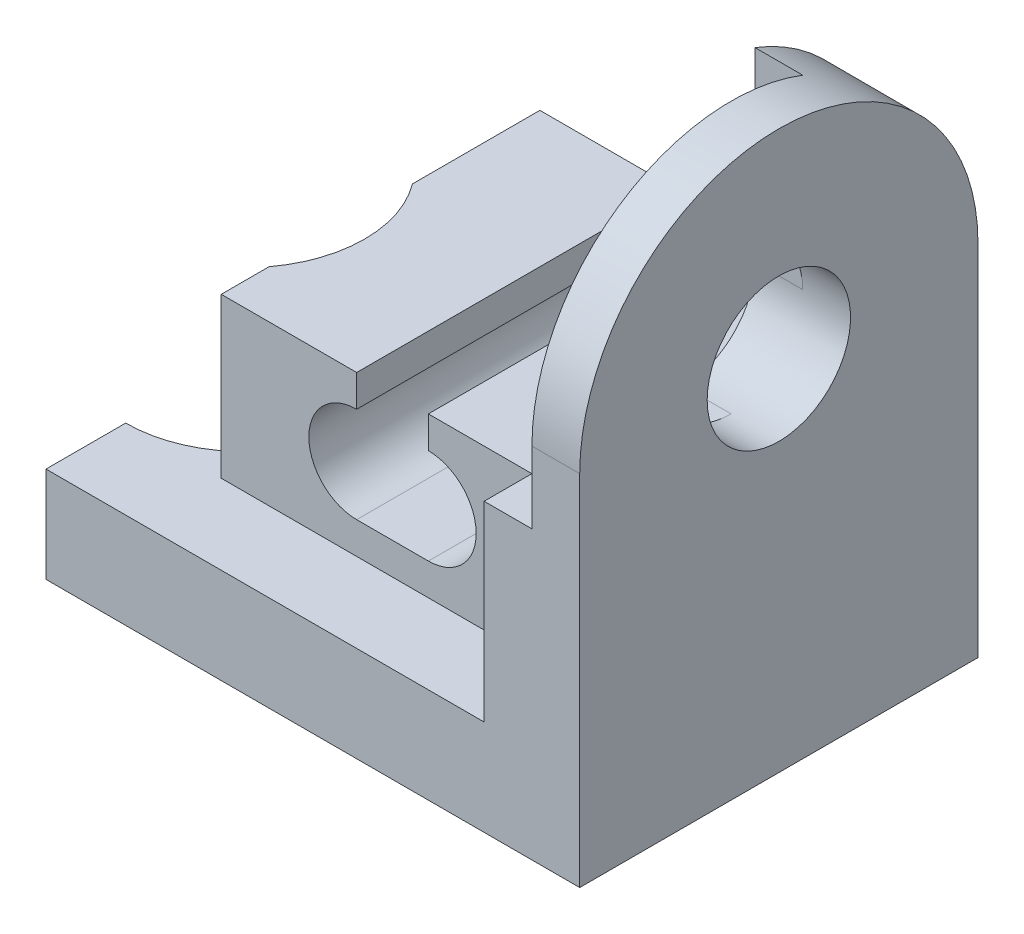
SolidWorks part; units mm, degrees
ref_plane "Front Plane" through (0, 0, 0) normal (0, 0, 1) x (1, 0, 0)
ref_plane "Top Plane" through (0, 0, 0) normal (0, 1, 0) x (1, 0, 0)
ref_plane "Right Plane" through (0, 0, 0) normal (1, 0, 0) x (0, 0, -1)
sketch "Sketch1" plane through (0, 0, 0) normal (0, 0, 1) x (1, 0, 0)
  line L0 (-38, 22) -> (-32, 22) construction
  line L1 (0, 0) -> (-67, 0)
  line L2 (0, 0) -> (0, 10.4431)
  line L3 (-12, 12) -> (-67, 12)
  line L4 (-67, 0) -> (-67, 12)
  line L5 (0, 0) -> (-14.6824, 0)
  line L6 (0, 0) -> (0, 70)
  line L7 (0, 70) -> (-12, 70)
  line L8 (-12, 12) -> (-12, 70)
  line L9 (-12, 12) -> (-55, 12)
  line L10 (-12, 12) -> (-12, 32)
  line L11 (-12, 32) -> (-29, 32)
  line L12 (-55, 12) -> (-55, 32)
  line L15 (-37.9992, 16) -> (-29, 16)
  line L17 (-29, 28) -> (-29, 32)
  line L18 (-38, 28) -> (-38, 32)
  line L19 (-38, 32) -> (-55, 32)
  arc A0 (-29, 16) -> (-29, 28) centre (-29, 22) ccw
  arc A1 (-38, 28) -> (-37.9992, 16) centre (-38, 22) ccw
  point P19 (-55, 22)
  dimension "D5" = 9
  dimension "D6" = 12
  dimension "D1" = 70
  dimension "D2" = 67
  dimension "D3" = 43
  dimension "D4" = 20
  dimension "D7" = 12
  dimension "D8" = 12
extrude "Boss-Extrude1" add sketch "Sketch1" along normal blind 25 and the other way blind 25 contours L8 L3 L4 L1 L2 L6 L7 region at (-7.3412, 0.969, 0)
extrude "Boss-Extrude2" add sketch "Sketch1<3>" against normal blind 25 and the other way blind 15 contours A1 L18 L19 L12 L3 L8 L11 L17 A0 L15 region at (-54.5258, 22, 0)
sketch "Sketch1<3>" plane through (0, 0, 0) normal (0, 0, 1) x (1, 0, 0) same geometry as "Sketch1"
sketch "Sketch2" plane through (0, 0, 0) normal (0, -1, 0) x (1, 0, 0)
  line L0 (-67, -25) -> (-67, 25) construction
  circle A0 centre (-67, 0) radius 15
  dimension "D1" = 30
extrude "Cut-Extrude1" cut sketch "Sketch2" against normal through all
sketch "Sketch3" plane through (-12, 0, 0) normal (-1, 0, 0) x (0, 0, 1)
  line L0 (-25, 45) -> (25, 45) construction
  line L1 (-9, 45) -> (-9, 68.3238)
  line L2 (0, 36) -> (23.3238, 36)
  line L3 (-9, 45) -> (25, 45)
  line L4 (23.3238, 36) -> (25, 36)
  line L5 (25, 12) -> (25, 70) construction
  line L6 (25, 36) -> (25, 45)
  arc A0 (25, 45) -> (-25, 45) centre (0, 45) ccw
  circle A1 centre (0, 45) radius 9
  point P7 (0, 45)
  line M10 (25, 12) -> (25, 70)
  line M11 (25, 70) -> (-25, 70)
  line M12 (-25, 70) -> (-25, 32)
  dimension "D1" = 45
  dimension "D2" = 50
  dimension "D3" = 18
extrude "Cut-Extrude2" cut sketch "Sketch3" against normal through all contours A0 M11 M12 | A0 M10 M11 region at (-12, 64.4158, -19.4158) region at (-12, 64.4158, 19.4158)
extrude "Cut-Extrude3" cut sketch "Sketch3<6>" against normal through all contours L3 A1 | L3 A1 region at (-12, 48.8197, 0) region at (-12, 41.1803, 0)
sketch "Sketch3<6>" plane through (-12, 0, 0) normal (-1, 0, 0) x (0, 0, 1) same geometry as "Sketch3"
extrude "Cut-Extrude4" cut sketch "Sketch3<7>" against normal blind 6 contours A1 L3 A0 L1 | A1 L2 A0 L3 region at (-12, 57.701, 7.2461) region at (-12, 40.2318, 15.9218)
sketch "Sketch3<7>" plane through (-12, 0, 0) normal (-1, 0, 0) x (0, 0, 1) same geometry as "Sketch3"
